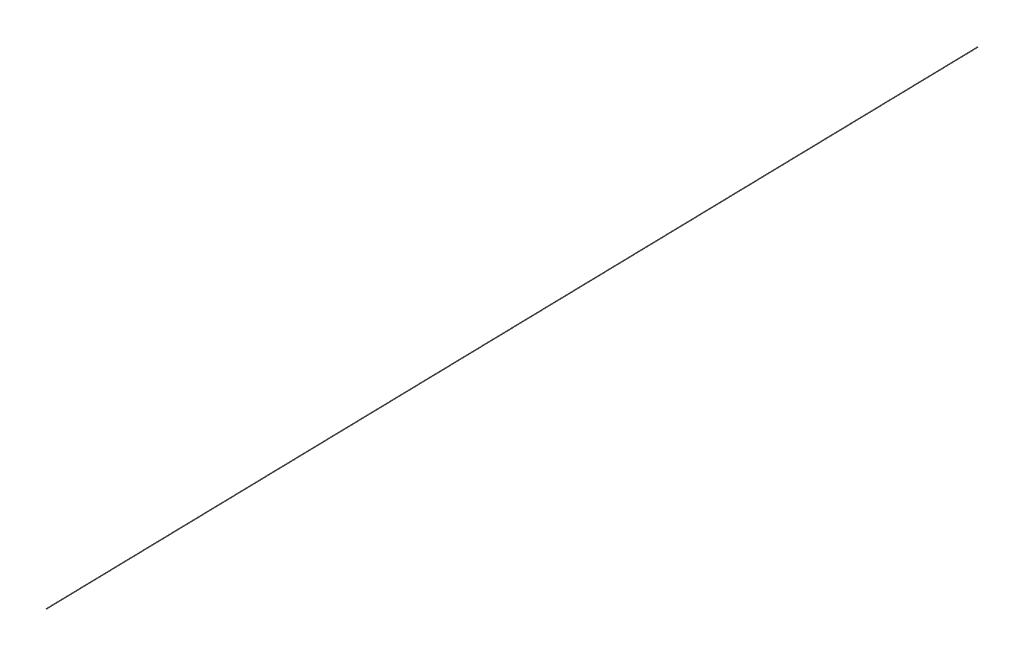
SolidWorks part; units mm, degrees
ref_plane "Front Plane" through (0, 0, 0) normal (0, 0, 1) x (1, 0, 0)
ref_plane "Top Plane" through (0, 0, 0) normal (0, 1, 0) x (1, 0, 0)
ref_plane "Right Plane" through (0, 0, 0) normal (1, 0, 0) x (0, 0, -1)
sketch "Sketch1" plane through (0, 0, 0) normal (1, 0, 0) x (0, 0, -1)
  line L0 (0, 0) -> (14563.8, 0) construction
  line L1 (14563.8, 0) -> (14563.8, 326.14) construction
  line L3 (14563.8, 326.14) -> (14553.8, 326.14)
  line L4 (0, 0) -> (10, 0)
  line L5 (10, 0) -> (14553.8, 326.14)
  dimension "D1" = 14563.8
  dimension "D2" = 10
  dimension "D3" = 10
  dimension "D4" = 326.14
sketch "Sketch2" plane through (0, 0, 0) normal (0, 0, 1) x (1, 0, 0)
  circle A0 centre (0, 0) radius 3.8
  dimension "D1" = 7.6
sweep "Sweep1" add profiles "Sketch2" path "Sketch1"
